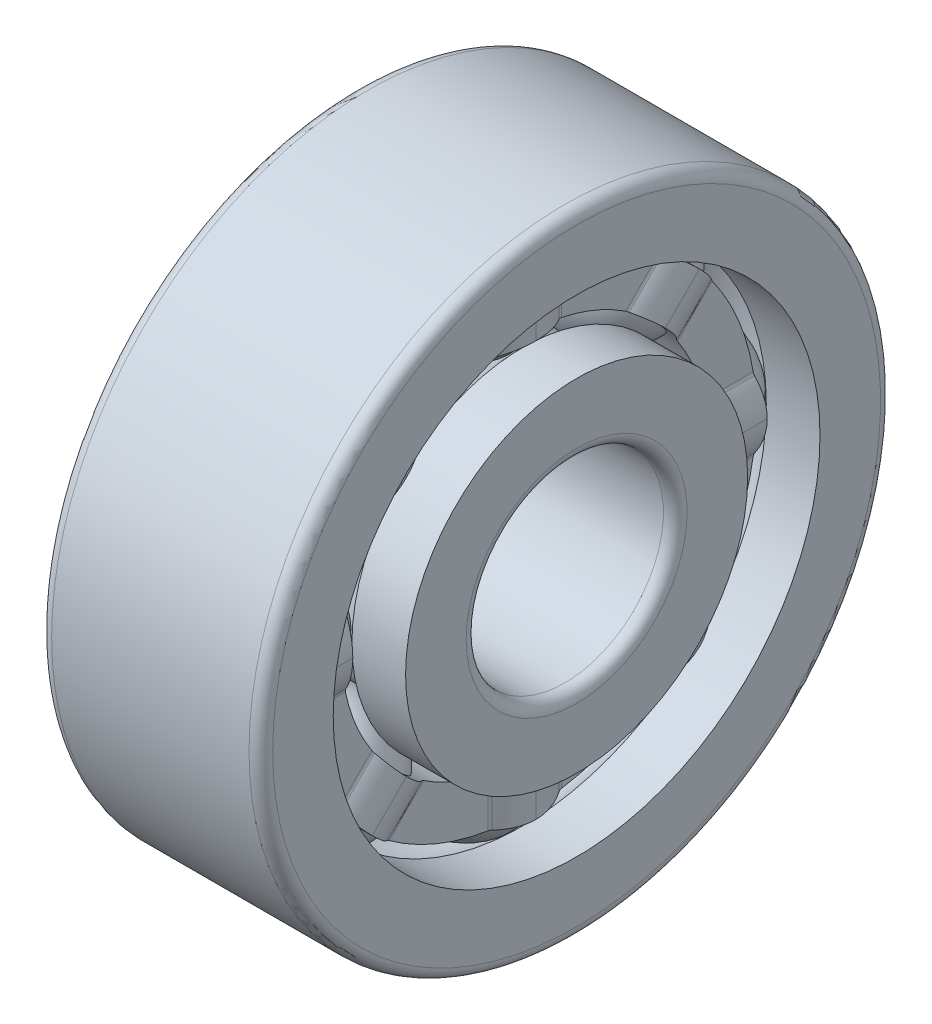
SolidWorks part; units mm, degrees
ref_plane "Front" through (0, 0, 0) normal (0, 0, 1) x (1, 0, 0)
ref_plane "Top" through (0, 0, 0) normal (0, 1, 0) x (1, 0, 0)
ref_plane "Right" through (0, 0, 0) normal (1, 0, 0) x (0, 0, -1)
sketch "Support-Front-Body" plane through (0, 0, 0) normal (0, 0, 1) x (1, 0, 0)
  line L0 (-1.4, 0) -> (1.4, 0) construction
  line L1 (1.4, 0) -> (1.4, 1.25) construction
  line L2 (-1.4, 0) -> (-1.4, 1.25) construction
  line L4 (-1.4, 4) -> (1.4, 4)
  line L5 (-1.4, 4) -> (-1.4, 3.0833)
  line L6 (-1.4, 3.0833) -> (1.4, 3.0833)
  line L7 (1.4, 4) -> (1.4, 3.0833)
  line L8 (-1.4, 2.1667) -> (1.4, 2.1667)
  line L9 (-1.4, 2.1667) -> (-1.4, 1.25)
  line L10 (-1.4, 1.25) -> (1.4, 1.25)
  line L11 (1.4, 2.1667) -> (1.4, 1.25)
  line L13 (-1.4, 2.625) -> (1.4, 2.625) construction
  line L14 (0, 0) -> (0, 1.25) construction
  line L15 (0, 1.25) -> (0, 2.1667) construction
  line L16 (0, 2.1667) -> (0, 3.0833) construction
  line L17 (0, 3.0833) -> (0, 4) construction
  dimension "Diam-Inner" = 2.5
  dimension "Diam-Outer" = 8
  dimension "CC-Ball" = 5.25
  dimension "Width-Inner" = 2.8
sketch "Support-Front-Ball" plane through (0, 0, 0) normal (0, 0, 1) x (1, 0, 0)
  line L0 (-0.825, 2.625) -> (0.825, 2.625) construction
  line L1 (0, 0) -> (0, 1.8) construction
  line L2 (-1.4, 2.625) -> (1.4, 2.625) construction
  line L3 (0, 2.625) -> (0, 3.45) construction
  line L6 (0, 1.8) -> (0, 2.625) construction
  circle A0 centre (0, 2.625) radius 0.825
  dimension "Diam-Ball" = 1.65
sketch "Support-Front-Groove" plane through (0, 0, 0) normal (0, 0, 1) x (1, 0, 0)
  line L0 (0, 3.0833) -> (0, 2.9306) construction
  line L1 (0, 2.9306) -> (0, 2.7778) construction
  line L2 (0, 2.7778) -> (0, 2.625) construction
  line L3 (-1.4, 2.625) -> (1.4, 2.625) construction
  line L4 (-0.825, 2.625) -> (0.825, 2.625) construction
  line L6 (-1.4, 3.0833) -> (1.4, 3.0833) construction
  line L7 (0, 1.8337) -> (0, 1.8) construction
  line L8 (0.686, 2.1667) -> (0.7196, 2.1667) construction
  line L9 (-1.4, 2.1667) -> (1.4, 2.1667) construction
  line L11 (0, 0) -> (0, 1.8) construction
  line L12 (-0.825, 2.625) -> (0.825, 2.625) construction
  circle A0 centre (0, 2.625) radius 0.825 construction
  circle A1 centre (0, 2.7778) radius 0.9441
  circle A2 centre (0, 2.4722) radius 0.9441
sketch "Support-Front-Ball-Cage" plane through (0, 0, 0) normal (0, 0, 1) x (1, 0, 0)
  line L0 (0.825, 2.625) -> (-0.884, 2.625) construction
  line L1 (-0.884, 2.9306) -> (0.884, 2.9306)
  line L2 (-0.884, 2.9306) -> (-0.884, 2.3194)
  line L3 (-0.884, 2.3194) -> (0.884, 2.3194)
  line L4 (0.884, 2.9306) -> (0.884, 2.3194)
  line L5 (-1.4, 2.625) -> (1.4, 2.625) construction
  line L6 (0, 2.3194) -> (0, 2.9306) construction
  line L7 (0, 2.1667) -> (0, 3.0833) construction
  line L8 (0.825, 2.625) -> (0.884, 2.625) construction
  line L9 (0.8545, 2.625) -> (0.8545, 2.7778) construction
  line L10 (0.8545, 2.7778) -> (0.8545, 2.9306) construction
  line L11 (0.8545, 2.9306) -> (0.8545, 3.0833) construction
  line L12 (-1.4, 3.0833) -> (1.4, 3.0833) construction
  line L13 (0.884, 3.0069) -> (0.7313, 3.0069) construction
  line L14 (0, 2.9306) -> (0, 3.509) construction
  circle A0 centre (0, 2.625) radius 0.825 construction
  circle A1 centre (0, 2.625) radius 0.884 construction
  point P26 (0.8545, 3.0069)
sketch "Support-Right-Ball-Cage" plane through (0, 0, 0) normal (1, 0, 0) x (0, 0, -1)
  line L0 (0, 0) -> (0, 4) construction
  line L1 (0, 0) -> (-2.8284, 2.8284) construction
  line L2 (0, 1.741) -> (-1.231, 1.231) construction
  line L3 (-2.4813, 2.4813) -> (0, 3.509) construction
  line L4 (0, 0) -> (-1.7107, 3.6158) construction
  line L6 (-1.3471, 3.7663) -> (0, 0) construction
  circle A0 centre (0, 0) radius 2.3194
  circle A1 centre (0, 0) radius 2.9306
  circle A2 centre (0, 2.625) radius 0.884
  circle A3 centre (0, 0) radius 2.625 construction
  circle A4 centre (-1.8562, 1.8562) radius 0.884
  dimension "Angle-Ball" = 45
ref_plane "Ref-Plane-1" through (0, 1.486, 0.6155) normal (0, 0.9239, 0.3827) x (-1, 0, 0)
sketch "Support-Ball-Gage-Inner" plane through (0, 1.486, 0.6155) normal (0, 0.9239, 0.3827) x (-1, 0, 0)
  line L0 (-0.7431, -0.1638) -> (-0.7431, 0.1638)
  line L1 (0.7431, -0.1638) -> (0.7431, 0.1638)
  line L2 (0.884, 0.6662) -> (0.884, -0.6662)
  line L3 (-0.884, 0) -> (-0.7431, 0) construction
  line L4 (-0.825, -1.0045) -> (-0.825, -0.1638) construction
  line L5 (-0.825, -0.1638) -> (-0.7431, -0.1638) construction
  line L6 (-0.825, -0.1638) -> (-0.825, -0.0819) construction
  line L7 (-0.825, -0.0819) -> (-0.825, 0) construction
  line L8 (-0.7431, 0) -> (0, 0) construction
  line L9 (-0.884, 0.6662) -> (-0.884, -0.6662)
  line L10 (-0.884, -1.1215) -> (-0.884, -0.8876) construction
  line L11 (-0.825, -0.0819) -> (-0.7431, -0.1638) construction
  line L12 (0, 0.6662) -> (0, -0.6662) construction
  arc A0 (-0.884, -0.6662) -> (-0.755, -0.2064) centre (0, -0.6662) cw
  arc A1 (-0.755, -0.2064) -> (-0.7431, -0.1638) centre (-0.825, -0.1638) ccw
  arc A2 (-0.7431, 0.1638) -> (-0.755, 0.2064) centre (-0.825, 0.1638) ccw
  arc A3 (-0.755, 0.2064) -> (-0.884, 0.6662) centre (0, 0.6662) cw
  arc A4 (0.755, 0.2064) -> (0.884, 0.6662) centre (0, 0.6662) ccw
  arc A5 (0.7431, 0.1638) -> (0.755, 0.2064) centre (0.825, 0.1638) cw
  arc A6 (0.755, -0.2064) -> (0.7431, -0.1638) centre (0.825, -0.1638) cw
  arc A7 (0.884, -0.6662) -> (0.755, -0.2064) centre (0, -0.6662) ccw
  dimension "D1" = 45
ref_plane "Ref-Plane-2" through (0, 2.9952, 1.2406) normal (0, -0.9239, -0.3827) x (1, 0, 0)
sketch "Support-Ball-Gage-Outer" plane through (0, 2.9952, 1.2406) normal (0, -0.9239, -0.3827) x (1, 0, 0)
  line L0 (0.884, 1.3429) -> (0.884, -1.3429)
  line L1 (0.7431, -0.8404) -> (0.7431, 0.8404)
  line L2 (0.884, 0.6662) -> (0.884, -0.6662) construction
  line L7 (0.7431, -0.1638) -> (0.7431, 0.1638) construction
  line L8 (0, 1.3429) -> (0, -1.3429) construction
  line L9 (-0.884, 1.3429) -> (-0.884, -1.3429)
  line L10 (-0.7431, -0.8404) -> (-0.7431, 0.8404)
  arc A0 (0.884, -1.3429) -> (0.755, -0.883) centre (0, -1.3429) ccw
  arc A1 (0.755, -0.883) -> (0.7431, -0.8404) centre (0.825, -0.8404) cw
  arc A2 (0.7431, 0.8404) -> (0.755, 0.883) centre (0.825, 0.8404) cw
  arc A3 (0.755, 0.883) -> (0.884, 1.3429) centre (0, 1.3429) ccw
  arc A4 (0.755, 0.2064) -> (0.7431, 0.1638) centre (0.825, 0.1638) ccw construction
  arc A5 (-0.755, -0.883) -> (-0.7431, -0.8404) centre (-0.825, -0.8404) ccw
  arc A6 (-0.884, -1.3429) -> (-0.755, -0.883) centre (0, -1.3429) cw
  arc A7 (-0.755, 0.883) -> (-0.884, 1.3429) centre (0, 1.3429) cw
  arc A8 (-0.7431, 0.8404) -> (-0.755, 0.883) centre (-0.825, 0.8404) ccw
ref_axis "Ref-Axis" through (-2.75, 0, 0) along (1, 0, 0)
ref_plane "Ref-Plane-Right" through (1.4, 0, 0) normal (1, 0, 0) x (0, 0, -1)
ref_plane "Ref-Plane-Left" through (-1.4, 0, 0) normal (1, 0, 0) x (0, 0, -1)
sketch "Sketch7" plane through (0, 0, 0) normal (0, 0, 1) x (1, 0, 0)
  line L0 (-0.825, 2.625) -> (0.825, 2.625) construction
  line L2 (-0.825, 2.625) -> (0.825, 2.625) construction
  line L4 (-0.825, 2.625) -> (0.825, 2.625)
  circle A0 centre (0, 2.625) radius 0.825 construction
  arc A1 (-0.825, 2.625) -> (0.825, 2.625) centre (0, 2.625) ccw
revolve "Body-Ball" add sketch "Sketch7" angle 360 about L2
sketch "Sketch10" plane through (0, 0, 0) normal (0, 0, 1) x (1, 0, 0)
  line L0 (-1.4, 0) -> (1.4, 0) construction
  line L1 (-0.884, 2.9306) -> (-0.884, 2.3194) construction
  line L2 (-0.884, 2.9306) -> (0.884, 2.9306) construction
  line L3 (0.884, 2.9306) -> (0.884, 2.3194) construction
  line L4 (-0.884, 2.3194) -> (0.884, 2.3194) construction
  line L5 (-1.4, 0) -> (1.4, 0) construction
  line L6 (-0.884, 2.9306) -> (-0.884, 2.3194)
  line L7 (-0.884, 2.9306) -> (0.884, 2.9306)
  line L8 (0.884, 2.9306) -> (0.884, 2.3194)
  line L9 (-0.884, 2.3194) -> (0.884, 2.3194)
revolve "Body-Ball-Cage" add sketch "Sketch10" angle 360 about L5
sketch "Sketch16" plane through (0, 1.486, 0.6155) normal (0, 0.9239, 0.3827) x (-1, 0, 0)
  line L0 (0.7431, -0.1638) -> (0.7431, 0.1638) construction
  line L1 (0.884, 0.6662) -> (0.884, -0.6662) construction
  line L2 (0.7431, -0.1638) -> (0.7431, 0.1638)
  line L3 (0.884, 0.6662) -> (0.884, -0.6662)
  arc A0 (0.755, 0.2064) -> (0.884, 0.6662) centre (0, 0.6662) ccw construction
  arc A1 (0.755, 0.2064) -> (0.7431, 0.1638) centre (0.825, 0.1638) ccw construction
  arc A2 (0.7431, -0.1638) -> (0.755, -0.2064) centre (0.825, -0.1638) ccw construction
  arc A3 (0.884, -0.6662) -> (0.755, -0.2064) centre (0, -0.6662) ccw construction
  arc A4 (0.755, 0.2064) -> (0.884, 0.6662) centre (0, 0.6662) ccw
  arc A5 (0.755, 0.2064) -> (0.7431, 0.1638) centre (0.825, 0.1638) ccw
  arc A6 (0.7431, -0.1638) -> (0.755, -0.2064) centre (0.825, -0.1638) ccw
  arc A7 (0.884, -0.6662) -> (0.755, -0.2064) centre (0, -0.6662) ccw
sketch "Sketch17" plane through (0, 2.9952, 1.2406) normal (0, -0.9239, -0.3827) x (1, 0, 0)
  line L0 (-0.7431, -0.8404) -> (-0.7431, 0.8404) construction
  line L1 (-0.884, 1.3429) -> (-0.884, -1.3429) construction
  line L2 (-0.7431, -0.8404) -> (-0.7431, 0.8404)
  line L3 (-0.884, 1.3429) -> (-0.884, -1.3429)
  arc A0 (-0.884, 1.3429) -> (-0.755, 0.883) centre (0, 1.3429) ccw construction
  arc A1 (-0.7431, 0.8404) -> (-0.755, 0.883) centre (-0.825, 0.8404) ccw construction
  arc A2 (-0.755, -0.883) -> (-0.7431, -0.8404) centre (-0.825, -0.8404) ccw construction
  arc A3 (-0.755, -0.883) -> (-0.884, -1.3429) centre (0, -1.3429) ccw construction
  arc A4 (-0.884, 1.3429) -> (-0.755, 0.883) centre (0, 1.3429) ccw
  arc A5 (-0.7431, 0.8404) -> (-0.755, 0.883) centre (-0.825, 0.8404) ccw
  arc A6 (-0.755, -0.883) -> (-0.7431, -0.8404) centre (-0.825, -0.8404) ccw
  arc A7 (-0.755, -0.883) -> (-0.884, -1.3429) centre (0, -1.3429) ccw
loft "Cut-Ball-Cage-1" cut profiles "Sketch16", "Sketch17"
sketch "Sketch14" plane through (0, 1.486, 0.6155) normal (0, 0.9239, 0.3827) x (-1, 0, 0)
  line L0 (-0.7431, -0.1638) -> (-0.7431, 0.1638) construction
  line L1 (-0.884, 0.6662) -> (-0.884, -0.6662) construction
  line L2 (-0.7431, -0.1638) -> (-0.7431, 0.1638)
  line L3 (-0.884, 0.6662) -> (-0.884, -0.6662)
  arc A0 (-0.884, 0.6662) -> (-0.755, 0.2064) centre (0, 0.6662) ccw construction
  arc A1 (-0.7431, 0.1638) -> (-0.755, 0.2064) centre (-0.825, 0.1638) ccw construction
  arc A2 (-0.755, -0.2064) -> (-0.7431, -0.1638) centre (-0.825, -0.1638) ccw construction
  arc A3 (-0.755, -0.2064) -> (-0.884, -0.6662) centre (0, -0.6662) ccw construction
  arc A4 (-0.884, 0.6662) -> (-0.755, 0.2064) centre (0, 0.6662) ccw
  arc A5 (-0.7431, 0.1638) -> (-0.755, 0.2064) centre (-0.825, 0.1638) ccw
  arc A6 (-0.755, -0.2064) -> (-0.7431, -0.1638) centre (-0.825, -0.1638) ccw
  arc A7 (-0.755, -0.2064) -> (-0.884, -0.6662) centre (0, -0.6662) ccw
sketch "Sketch15" plane through (0, 2.9952, 1.2406) normal (0, -0.9239, -0.3827) x (1, 0, 0)
  line L0 (0.7431, -0.8404) -> (0.7431, 0.8404) construction
  line L1 (0.884, 1.3429) -> (0.884, -1.3429) construction
  line L2 (0.7431, -0.8404) -> (0.7431, 0.8404)
  line L3 (0.884, 1.3429) -> (0.884, -1.3429)
  arc A0 (0.755, 0.883) -> (0.884, 1.3429) centre (0, 1.3429) ccw construction
  arc A1 (0.755, 0.883) -> (0.7431, 0.8404) centre (0.825, 0.8404) ccw construction
  arc A2 (0.7431, -0.8404) -> (0.755, -0.883) centre (0.825, -0.8404) ccw construction
  arc A3 (0.884, -1.3429) -> (0.755, -0.883) centre (0, -1.3429) ccw construction
  arc A4 (0.755, 0.883) -> (0.884, 1.3429) centre (0, 1.3429) ccw
  arc A5 (0.755, 0.883) -> (0.7431, 0.8404) centre (0.825, 0.8404) ccw
  arc A6 (0.7431, -0.8404) -> (0.755, -0.883) centre (0.825, -0.8404) ccw
  arc A7 (0.884, -1.3429) -> (0.755, -0.883) centre (0, -1.3429) ccw
loft "Cut-Ball-Cage-2" cut profiles "Sketch15", "Sketch14"
pattern_circular "Pattern-Ball" count 8 over 360 about axis through (-2.75, 0, 0) along (1, 0, 0) of "Body-Ball", "Cut-Ball-Cage-2", "Cut-Ball-Cage-1"
sketch "Sketch2" plane through (0, 0, 0) normal (0, 0, 1) x (1, 0, 0)
  line L4 (-1.4, 2.1667) -> (-1.4, 1.25) construction
  line L5 (-1.4, 2.1667) -> (1.4, 2.1667) construction
  line L6 (1.4, 2.1667) -> (1.4, 1.25) construction
  line L7 (-1.4, 1.25) -> (1.4, 1.25) construction
  line L8 (-1.4, 0) -> (1.4, 0) construction
  line L9 (-1.4, 0) -> (1.4, 0) construction
  line L10 (-1.4, 2.1667) -> (-1.4, 1.25)
  line L11 (-1.4, 2.1667) -> (-0.7196, 2.1667)
  line L12 (1.4, 2.1667) -> (1.4, 1.25)
  line L13 (-1.4, 1.25) -> (1.4, 1.25)
  line L14 (0.7196, 2.1667) -> (1.4, 2.1667)
  circle A1 centre (0, 2.7778) radius 0.9441 construction
  arc A2 (-0.7196, 2.1667) -> (0.7196, 2.1667) centre (0, 2.7778) ccw
sketch "Sketch8" plane through (0, 0, 0) normal (0, 0, 1) x (1, 0, 0)
  line L0 (-1.4, 0) -> (1.4, 0) construction
  line L1 (-1.4, 4) -> (-1.4, 3.0833) construction
  line L2 (-1.4, 3.0833) -> (1.4, 3.0833) construction
  line L3 (1.4, 4) -> (1.4, 3.0833) construction
  line L4 (-1.4, 0) -> (1.4, 0) construction
  line L9 (-1.4, 4) -> (1.4, 4) construction
  line L10 (-1.4, 4) -> (-1.4, 3.0833)
  line L11 (-1.4, 3.0833) -> (-0.7196, 3.0833)
  line L12 (1.4, 4) -> (1.4, 3.0833)
  line L13 (-1.4, 4) -> (1.4, 4)
  line L14 (0.7196, 3.0833) -> (1.4, 3.0833)
  circle A1 centre (0, 2.4722) radius 0.9441 construction
  arc A2 (0.7196, 3.0833) -> (-0.7196, 3.0833) centre (0, 2.4722) ccw
revolve "Body-Inner" add sketch "Sketch2" angle 360 about L9
revolve "Body-Outer" add sketch "Sketch8" angle 360 about L4
fillet "Cosmetic-Fillet-Outer-1" radius 0.15 1 edges at (-1.4, 0, 4)
fillet "Cosmetic-Fillet-Outer-2" radius 0.15 1 edges at (1.4, 0, 4)
fillet "Cosmetic-Fillet-Inner-1" radius 0.15 1 edges at (-1.4, 0, 1.25)
fillet "Cosmetic-Fillet-Inner-2" radius 0.15 1 edges at (1.4, 0, 1.25)
equation "\"Diam-Ball@Support-Front-Ball\"=(((\"Diam-Outer@Support-Front-Body\"-\"Diam-Inner@Support-Front-Body\")/2)*3)/5"
equation "\"Num-Ball@Pattern-Ball\"=INT((PI*(\"Diam-Outer@Support-Front-Body\"-((\"Diam-Outer@Support-Front-Body\"-\"Diam-Inner@Support-Front-Body\")/2)))/(\"Diam-Ball@Support-Front-Ball\"*1.2))"
equation "\"Angle-Ball@Support-Right-Ball-Cage\" = 360 / INT(((PI*(\"Diam-Outer@Support-Front-Body\"-((\"Diam-Outer@Support-Front-Body\"-\"Diam-Inner@Support-Front-Body\")/4)))/2)/\"Diam-Ball@Support-Front-Ball\")"
equation "\"Angle-Ball@Support-Right-Ball-Cage\" = 360 / \"Num-Ball@Pattern-Ball\""
